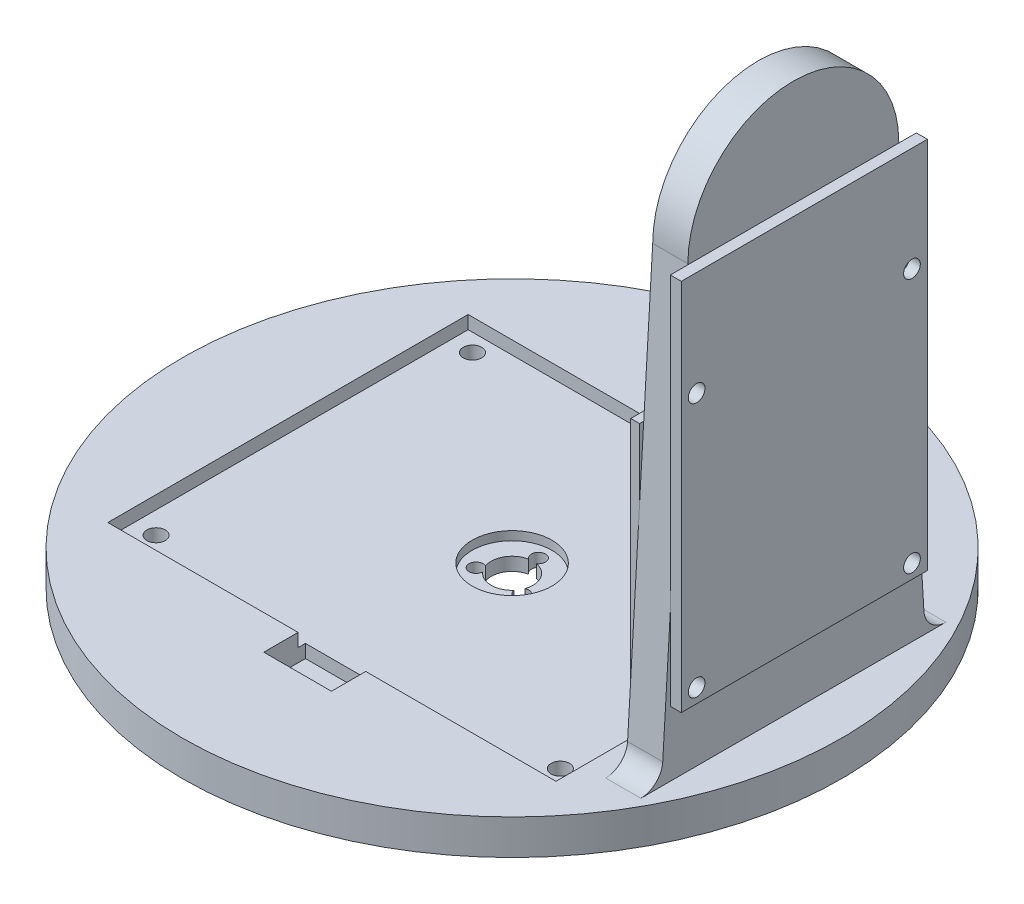
SolidWorks part; units mm, degrees
ref_plane "前视基准面" through (0, 0, 0) normal (0, 0, 1) x (1, 0, 0)
ref_plane "上视基准面" through (0, 0, 0) normal (0, 1, 0) x (1, 0, 0)
ref_plane "右视基准面" through (0, 0, 0) normal (1, 0, 0) x (0, 0, -1)
other "Configuration Table"
sketch "草图1" plane through (0, 0, 0) normal (0, 1, 0) x (1, 0, 0)
  line L1 (-51, 41) -> (51, 41)
  line L2 (-51, 41) -> (-51, -41)
  line L3 (-51, -41) -> (51, -41)
  line L4 (51, 41) -> (51, -41)
  line L5 (-51, 41) -> (51, -41) construction
  line L6 (-51, -41) -> (51, 41) construction
  circle A0 centre (0, 0) radius 75
  point P0 (0, 0)
  point P8 (50, -40)
  dimension "D1" = 82
  dimension "D2" = 102
extrude "凸台-拉伸2" add sketch "草图1" against normal blind 8 contours A0
extrude "切除-拉伸3" cut sketch "草图1<6>" against normal blind 3 contours L1 L4 L3 L2
sketch "草图1<6>" plane through (0, 0, 0) normal (0, 1, 0) x (1, 0, 0) same geometry as "草图1"
sketch "草图2" plane through (0, -3, 0) normal (0, 1, 0) x (1, 0, 0)
  circle A1 centre (0, 0) radius 9.065
extrude "切除-拉伸4" cut sketch "草图2" against normal blind 2 contours A1
sketch "草图3" plane through (0, -5, 0) normal (0, 1, 0) x (1, 0, 0)
  circle A0 centre (0, 0) radius 6
  circle A1 centre (0, 6) radius 1.6
  circle A2 centre (5.1962, -3) radius 1.6
  circle A3 centre (-5.1962, -3) radius 1.6
  point P11 (0, 0)
  dimension "D1" = 3
extrude "切除-拉伸5" cut sketch "草图3" against normal blind 10 contours A2 | A3 | A1
sketch "草图11" plane through (0, -5, 0) normal (0, 1, 0) x (1, 0, 0)
  circle A0 centre (0, 0) radius 4.7555
extrude "切除-拉伸6" cut sketch "草图11" against normal blind 10 contours A0
sketch "草图12" plane through (0, -3, 0) normal (0, 1, 0) x (1, 0, 0)
  line L0 (0, 0) -> (0, 36.9804)
  line L1 (0, 36.9804) -> (-46, 36.9804)
  line L2 (-51, 41) -> (51, -41) construction
  line L3 (0, 36.9804) -> (46, 36.9804)
  line L4 (46, 36.9804) -> (46, -35.0196)
  circle A0 centre (-46, 36.9804) radius 2.1
  circle A1 centre (46, 36.9804) radius 2.1
  circle A2 centre (46, -35.0196) radius 2.1
  circle A3 centre (-46, -35.0196) radius 2.1
extrude "切除-拉伸7" cut sketch "草图12" against normal blind 10 contours A2 | A3 | A1 | A0
sketch "草图21" plane through (0, 0, 0) normal (0, 1, 0) x (1, 0, 0)
  line L1 (-7.6998, -39.3282) -> (7.6998, -39.3282)
  line L2 (-7.6998, -39.3282) -> (-7.6998, -48.8049)
  line L3 (-7.6998, -48.8049) -> (7.6998, -48.8049)
  line L4 (7.6998, -39.3282) -> (7.6998, -48.8049)
  line L5 (-7.6998, -39.3282) -> (7.6998, -48.8049) construction
  line L6 (-7.6998, -48.8049) -> (7.6998, -39.3282) construction
  point P0 (0, -44.0666)
  dimension "D1" = 9.4767
  dimension "D2" = 15.3996
extrude "切除-拉伸8" cut sketch "草图21" against normal blind 6
sketch "草图22" plane through (0, 0, 0) normal (0, 1, 0) x (1, 0, 0)
  line L0 (0, 0) -> (60, 0)
  line L2 (56, 30) -> (64, 30)
  line L3 (56, 30) -> (56, -30)
  line L4 (56, -30) -> (64, -30)
  line L5 (64, 30) -> (64, -30)
  line L6 (56, 30) -> (64, -30) construction
  line L7 (56, -30) -> (64, 30) construction
  dimension "D1" = 60
  dimension "D2" = 8
ref_plane "基准面8" through (64, 0, 0) normal (-1, 0, 0) x (0, 0, 1)
sketch "草图24" plane through (64, 0, 0) normal (-1, 0, 0) x (0, 0, 1)
  line L0 (-24, 100) -> (-30, 0)
  line L1 (-30, 0) -> (30, 0)
  line L2 (30, 0) -> (24, 100)
  arc A0 (-24, 100) -> (24, 100) centre (0, 100) cw
extrude "凸台-拉伸5" add sketch "草图24" along normal blind 8
sketch "草图30" plane through (64, 0, 0) normal (1, 0, 0) x (0, 0, -1)
  line L1 (-28, 99.7845) -> (28, 99.7845)
  line L2 (-28, 99.7845) -> (-28, 14.7845)
  line L3 (-28, 14.7845) -> (28, 14.7845)
  line L4 (28, 99.7845) -> (28, 14.7845)
  line L5 (-28, 99.7845) -> (28, 14.7845) construction
  line L6 (-28, 14.7845) -> (28, 99.7845) construction
  point P0 (0, 57.2845)
  dimension "D1" = 85
  dimension "D2" = 56
extrude "凸台-拉伸6" add sketch "草图30" along normal blind 2.5
sketch "草图31" plane through (66.5, 0, 0) normal (1, 0, 0) x (0, 0, -1)
  circle A0 centre (-24.5, 18) radius 1.9
  circle A1 centre (24.5, 18) radius 1.9
  circle A2 centre (24.5, 76) radius 1.9
  circle A3 centre (-24.5, 76) radius 1.9
extrude "切除-拉伸10" cut sketch "草图31" against normal blind 3.5
fillet "圆角1" radius 5 2 edges at (60, 0, 30) (60, 0, -30)
sketch "草图40" plane through (56, 0, 0) normal (-1, 0, 0) x (0, 0, 1)
  line L1 (-25, 66.0065) -> (27, 66.0065)
  line L2 (-25, 66.0065) -> (-25, 14.0065)
  line L3 (-25, 14.0065) -> (27, 14.0065)
  line L4 (27, 66.0065) -> (27, 14.0065)
  line L5 (-25, 66.0065) -> (27, 14.0065) construction
  line L6 (-25, 14.0065) -> (27, 66.0065) construction
  point P0 (1, 40.0065)
  dimension "D1" = 52
sketch "草图41" plane through (56, 0, 0) normal (-1, 0, 0) x (0, 0, 1)
  line L0 (-25, 66.0065) -> (27, 14.0065) construction
  line L1 (-22.2, 63.2065) -> (24.2, 63.2065)
  line L2 (-22.2, 63.2065) -> (-22.2, 16.8065)
  line L3 (-22.2, 16.8065) -> (24.2, 16.8065)
  line L4 (24.2, 63.2065) -> (24.2, 16.8065)
  line L5 (-22.2, 63.2065) -> (24.2, 16.8065) construction
  line L6 (-22.2, 16.8065) -> (24.2, 63.2065) construction
  point P0 (1, 40.0065)
  dimension "D1" = 46.4
extrude "凸台-拉伸7" add sketch "草图40" along normal blind 2 contours L1 L4 L3 L2
sketch "草图42" plane through (54, 0, 0) normal (-1, 0, 0) x (0, 0, 1)
  circle A0 centre (-22.2, 63.2065) radius 1.9
  circle A1 centre (24.2, 63.2065) radius 1.9
  circle A2 centre (-22.2, 16.8065) radius 1.9
  circle A3 centre (24.2, 16.8065) radius 1.9
extrude "切除-拉伸11" cut sketch "草图42" against normal blind 3.5
sketch "草图52" plane through (56, 0, 0) normal (-1, 0, 0) x (0, 0, 1)
  circle A0 centre (0, 100) radius 15
  circle A1 centre (0, 115) radius 2.1
  circle A2 centre (10.6066, 110.6066) radius 2.1
  circle A3 centre (15, 100) radius 2.1
  circle A4 centre (10.6066, 89.3934) radius 2.1
  circle A5 centre (0, 85) radius 2.1
  circle A6 centre (-10.6066, 89.3934) radius 2.1
  circle A7 centre (-15, 100) radius 2.1
  circle A8 centre (-10.6066, 110.6066) radius 2.1
  point P21 (0, 100)
  dimension "D1" = 8
extrude "切除-拉伸12" cut sketch "草图52" against normal blind 4 contours A4 | A2 | A6 | A8
